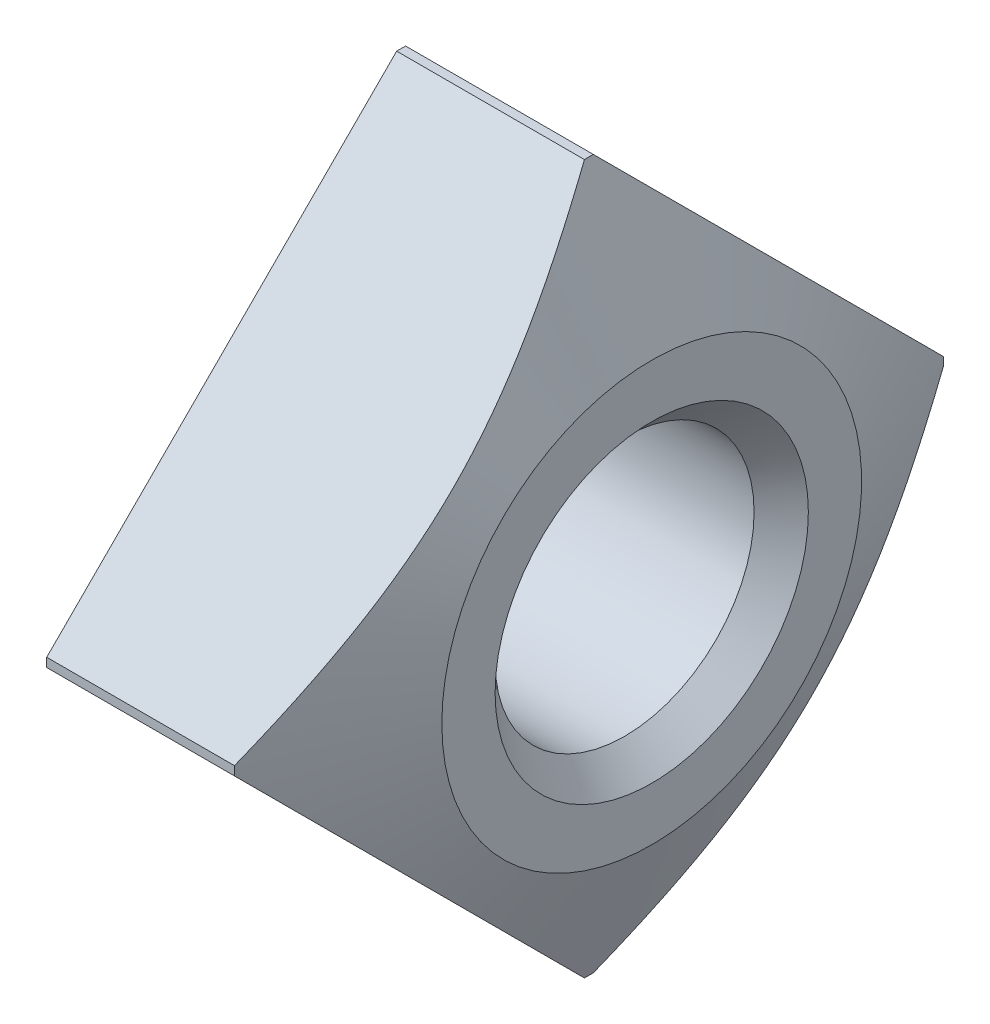
SolidWorks part; units mm, degrees
ref_plane "Front Plane" through (0, 0, 0) normal (0, 0, 1) x (1, 0, 0)
ref_plane "Top Plane" through (0, 0, 0) normal (0, 1, 0) x (1, 0, 0)
ref_plane "Right Plane" through (0, 0, 0) normal (1, 0, 0) x (0, 0, -1)
sketch "Sketch1" plane through (0, 0, 0) normal (0, 0, 1) x (1, 0, 0)
  line L0 (0, 0) -> (0, 5.6569)
  line L1 (0, 5.6569) -> (2.997, 5.6569)
  line L2 (2.997, 5.6569) -> (4, 3.35)
  line L3 (4, 3.35) -> (4, 0)
  line L4 (4, 0) -> (0, 0)
  line L5 (4, 0) -> (0, 0) construction
revolve "Revolve1" add sketch "Sketch1" angle 360 about L5 reverse direction yes
sketch "Sketch2" plane through (0, 0, 0) normal (1, 0, 0) x (0, 0, -1)
  line L0 (-16, 16) -> (-16, -16)
  line L1 (-16, -16) -> (16, -16)
  line L2 (16, -16) -> (16, 16)
  line L3 (16, 16) -> (-16, 16)
  line L4 (-5.7276, 0) -> (0, -5.7276)
  line L5 (0, -5.7276) -> (5.7276, 0)
  line L6 (5.7276, 0) -> (0, 5.7276)
  line L7 (0, 5.7276) -> (-5.7276, 0)
extrude "Cut-Extrude1" cut sketch "Sketch2" along normal blind 4
sketch "Sketch3" plane through (0, 0, 0) normal (0, 0, 1) x (1, 0, 0)
  line L0 (0, 0) -> (0, 2.5)
  line L1 (0, 2.5) -> (0.433, 2.067)
  line L2 (0.433, 2.067) -> (3.567, 2.067)
  line L3 (3.567, 2.067) -> (4, 2.5)
  line L4 (4, 2.5) -> (4, 0)
  line L5 (4, 0) -> (0, 0)
  line L6 (4, 0) -> (0, 0) construction
revolve "Cut-Revolve1" cut sketch "Sketch3" angle 360 about L6 reverse direction yes
cosmetic thread "Cosmetic Thread1" parameters "D1"=4, "D2"=5
ref_plane "Plane1" through (4, 0, 0) normal (1, 0, 0) x (0, 0, -1)
ref_plane "IP1 XY" through (0, 0, 0) normal (1, 0, 0) x (0, 0, -1)
ref_plane "IP1 XZ" through (0, 0, 0) normal (0, -1, 0) x (-1, 0, 0)
ref_plane "IP1 YZ" through (0, 0, 0) normal (0, 0, -1) x (-1, 0, 0)
ref_axis "IP1 X" through (0, 0, 80.9) along (0, 0, -1)
ref_axis "IP1 Y" through (0, -50, 0) along (0, 1, 0)
ref_axis "IP1 Z" through (80.9, 0, 0) along (-1, 0, 0)
sketch3d "IP1"
  point P0 (0, 0, 0)
ref_plane "IP2 XY" through (4, 0, 0) normal (1, 0, 0) x (0, 0, -1)
ref_plane "IP2 XZ" through (0, 0, 0) normal (0, -1, 0) x (-1, 0, 0)
ref_plane "IP2 YZ" through (0, 0, 0) normal (0, 0, -1) x (-1, 0, 0)
ref_axis "IP2 X" through (4, 0, 80.9) along (0, 0, -1)
ref_axis "IP2 Y" through (4, -50, 0) along (0, 1, 0)
ref_axis "IP2 Z" through (80.9, 0, 0) along (-1, 0, 0)
sketch3d "IP2"
  point P0 (4, 0, 0)
other "Freeze***"
